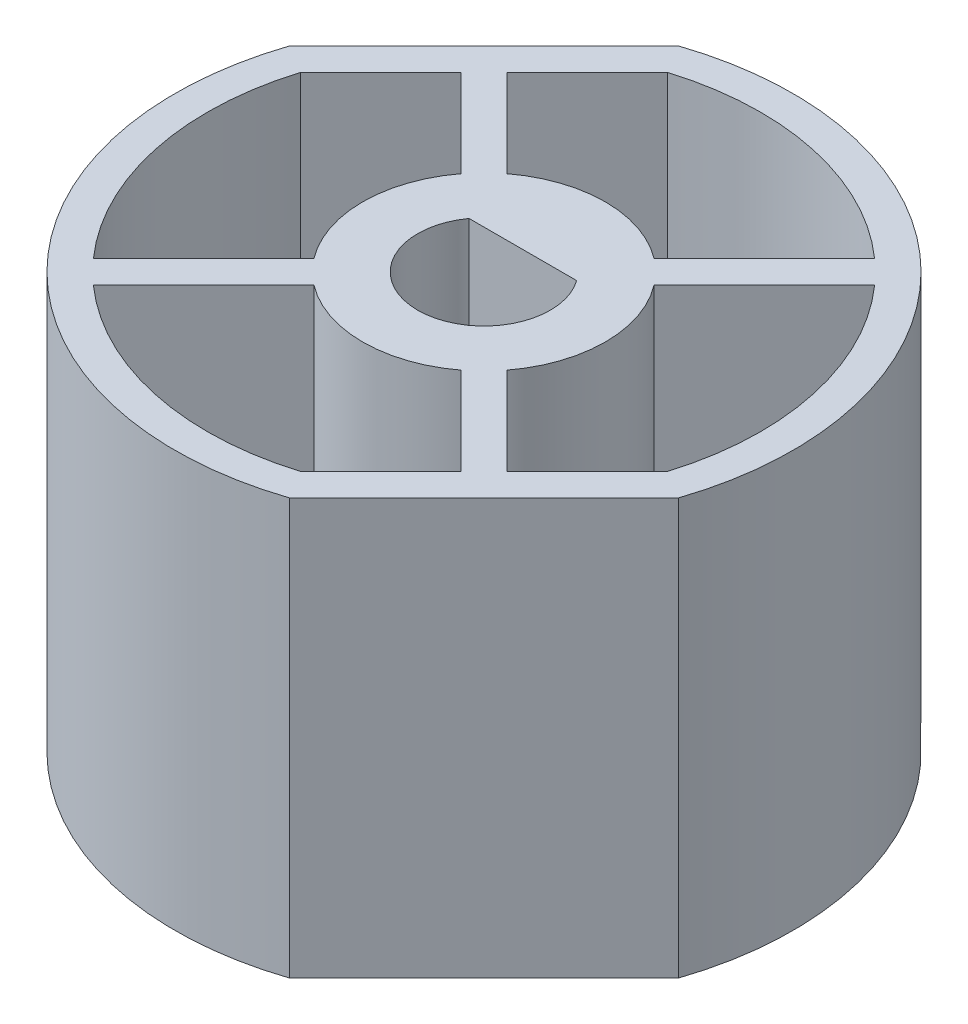
SolidWorks part; units mm, degrees
ref_plane "前视基准面" through (0, 0, 0) normal (0, 0, 1) x (1, 0, 0)
ref_plane "上视基准面" through (0, 0, 0) normal (0, 1, 0) x (1, 0, 0)
ref_plane "右视基准面" through (0, 0, 0) normal (1, 0, 0) x (0, 0, -1)
other "Configuration Table"
sketch "草图1" plane through (0, 0, 0) normal (0, 1, 0) x (1, 0, 0)
  line L0 (-3.3242, 2.4) -> (3.3242, 2.4)
  line L13 (-4.5768, -4.1) -> (14.7391, -4.1) construction
  line L14 (3.8348, 3.8348) -> (-5.8283, -5.8283) construction
  line L15 (13.435, 14.8492) -> (2.8284, 4.2426)
  line L32 (2.8284, 4.2426) -> (4.2426, 2.8284)
  line L33 (4.2426, 2.8284) -> (14.8492, 13.435)
  line L34 (14.8492, 13.435) -> (13.435, 14.8492)
  circle A14 centre (0, 0) radius 19.1
  circle A15 centre (0, 0) radius 16.6
  circle A16 centre (0, 0) radius 7.5
  circle A17 centre (0, 0) radius 4.1
  circle A18 centre (3.5355, 3.5355) radius 2
  dimension "D3" = 15
  dimension "D4" = 8.2
  dimension "D1" = 38.2
  dimension "D2" = 2.5
  dimension "D9" = 4
  dimension "D5" = 6.5
  dimension "D6" = 45
  dimension "D7" = 2
  dimension "D8" = 5
  dimension "D10" = 15
extrude "凸台-拉伸1" add sketch "草图1" along normal blind 25.7 contours A14
extrude "切除-拉伸1" cut sketch "草图1<7>" along normal blind 2 contours L33 L34 L15 L32 | A18
sketch "草图1<7>" plane through (0, 0, 0) normal (0, 1, 0) x (1, 0, 0) same geometry as "草图1"
sketch "草图2" plane through (0, 0, 0) normal (0, -1, 0) x (1, 0, 0)
  line L0 (-6.0749, -18.1082) -> (-18.1082, -6.0749)
  line L1 (5.4674, -4.0532) -> (14.1943, -12.7801) construction
  line L2 (6.0749, 18.1082) -> (18.1082, 6.0749)
  line L3 (-12.0915, -12.0915) -> (12.0915, 12.0915)
  line L4 (22.3153, 4.6961) -> (-0.8075, 27.819) construction
  line L5 (-18.1082, -6.0749) -> (6.0749, 18.1082)
  line L6 (18.1082, 6.0749) -> (-6.0749, -18.1082)
  arc A0 (14.1943, -12.7801) -> (12.7801, -14.1943) centre (0, 0) ccw construction
  arc M6 (14.1943, -12.7801) -> (12.7801, -14.1943) centre (0, 0) ccw
  dimension "D1" = 2
extrude "切除-拉伸2" cut sketch "草图2" against normal through all contours L2 M6 | L0 M6 region at (-12.6598, 0, -12.6598) region at (12.6598, 0, 12.6598)
sketch "草图3" plane through (0, 25.7, 0) normal (0, 1, 0) x (1, 0, 0)
  line L0 (-5.0028, 16.3518) -> (-16.3518, 5.0028)
  line L1 (16.3518, -5.0028) -> (5.0028, -16.3518)
  line L2 (-6.0749, 18.1082) -> (-18.1082, 6.0749) construction
  line L3 (6.0749, -18.1082) -> (18.1082, -6.0749) construction
  circle A0 centre (0, 0) radius 17.1
  arc A1 (18.1082, -6.0749) -> (-6.0749, 18.1082) centre (0, 0) ccw construction
  dimension "D1" = 2
  dimension "D2" = 2
  dimension "D3" = 2
extrude "切除-拉伸3" cut sketch "草图3" against normal offset from surface (21.7 mm away) 2 contours L1 A0 L0 region at (0, 25.7, 0) up to face at (8.4686, 2, -8.4686)
extrude "凸台-拉伸2" add sketch "草图1<8>" along normal up to surface (25.7 mm away) from surface contours A18 A17 L15 A16 L33 | A18 L0 A17 | A17 A18 L33 L32 L15 | L0 A18 A17 | L33 A18 L15 L32 | A18 L33 A16 L15 region at (-0.4676, 0, -3.127) region at (-1.3264, 0, 4.1031) region at (2.239, 0, -2.9348) region at (3.5057, 0, -3.5057) region at (4.2131, 0, -4.2131) region at (5.0843, 0, -5.0843) up to face at (0, 25.7, 0) starting at face at (0, 4, 0)
sketch "草图1<8>" plane through (0, 0, 0) normal (0, 1, 0) x (1, 0, 0) same geometry as "草图1"
sketch "草图4" plane through (0, 25.7, 0) normal (0, 1, 0) x (1, 0, 0)
  line L0 (-10.6773, 10.6773) -> (-3.6062, 3.6062)
  line L1 (-5.0028, 16.3518) -> (-16.3518, 5.0028) construction
  line L2 (5.0028, -16.3518) -> (16.3518, -5.0028) construction
  line L3 (12.0915, 12.0915) -> (4.3134, 4.3134)
  line L4 (16.3518, -5.0028) -> (5.0028, -16.3518) construction
  line L5 (-4.3134, -4.3134) -> (-12.0915, -12.0915)
  line L6 (3.6062, -3.6062) -> (10.6773, -10.6773)
  arc A0 (16.3518, -5.0028) -> (-5.0028, 16.3518) centre (0, 0) ccw construction
  arc A1 (-16.3518, 5.0028) -> (5.0028, -16.3518) centre (0, 0) ccw construction
  dimension "D1" = 11
  dimension "D2" = 10
extrude "拉伸-薄壁3" add sketch "草图4" against normal up to surface (21.7 mm away) thin up to face at (0, 4, 7.5) thin type mid plane wall 2
